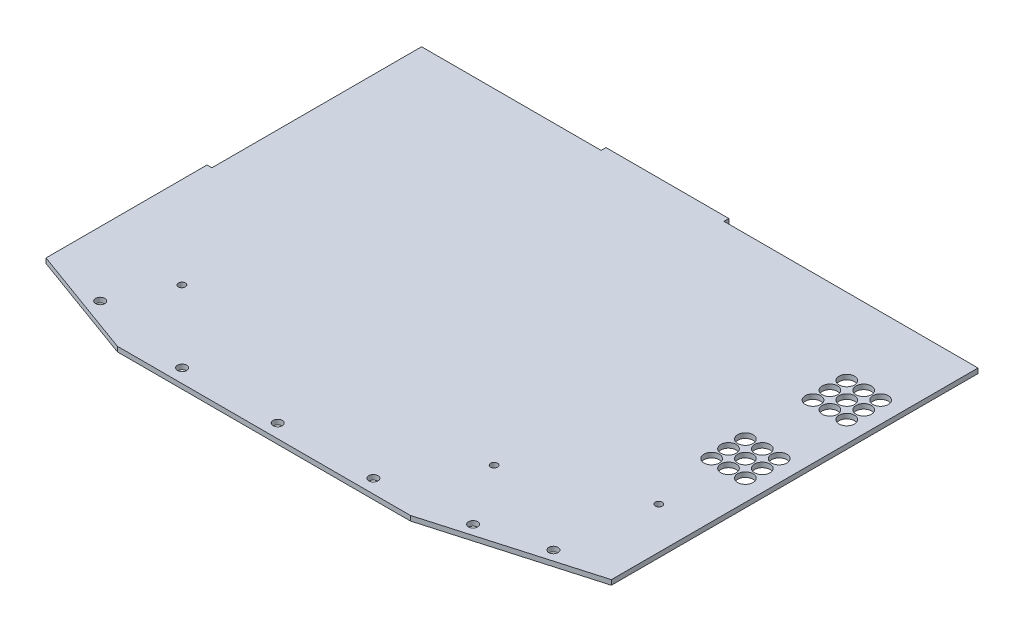
SolidWorks part; units mm, degrees
material "6061-T6 (SS)"
ref_plane "X-Y Datum" through (0, 0, 0) normal (0, 0, 1) x (1, 0, 0)
ref_plane "X-Z Datum" through (0, 0, 0) normal (0, 1, 0) x (1, 0, 0)
ref_plane "Y-Z Datum" through (0, 0, 0) normal (1, 0, 0) x (0, 0, -1)
sketch "Sketch1" plane through (0, 0, 0) normal (0, 0, 1) x (1, 0, 0)
  line L1 (-154.0556, -1.5875) -> (154.0556, -1.5875)
  line L2 (-154.0556, -1.5875) -> (-154.0556, 1.5875)
  line L3 (-154.0556, 1.5875) -> (154.0556, 1.5875)
  line L4 (154.0556, -1.5875) -> (154.0556, 1.5875)
  line L5 (-154.0556, -1.5875) -> (154.0556, 1.5875) construction
  line L6 (-154.0556, 1.5875) -> (154.0556, -1.5875) construction
  point P0 (0, 0)
  dimension "D1" = 3.175
  dimension "D2" = 308.1112
extrude "Boss-Extrude1" add sketch "Sketch1" along normal blind 267.83
sketch "Sketch3" plane through (154.0556, 0, 0) normal (1, 0, 0) x (0, 0, -1)
  line L9 (0, -1.5875) -> (0, 1.5875)
  line L10 (0, 1.5875) -> (-267.83, 1.5875)
  line L11 (-267.83, 1.5875) -> (-267.83, -1.5875)
  line L12 (-267.83, -1.5875) -> (0, -1.5875)
  line L13 (0, -1.5875) -> (0, 1.5875)
  line L14 (0, 1.5875) -> (-267.83, 1.5875)
  line L15 (-267.83, 1.5875) -> (-267.83, -1.5875)
  line L16 (-267.83, -1.5875) -> (0, -1.5875)
  dimension "D1" = 0
extrude "Boss-Extrude3" add sketch "Sketch3" along normal blind 3.175
sketch "Sketch4" plane through (0, 0, 267.83) normal (0, 0, 1) x (1, 0, 0)
  line L1 (157.2306, -1.5875) -> (208.1043, -1.5875)
  line L2 (157.2306, -1.5875) -> (157.2306, 1.5875)
  line L3 (157.2306, 1.5875) -> (208.1043, 1.5875)
  line L4 (208.1043, -1.5875) -> (208.1043, 1.5875)
  dimension "D1" = 3.175
  dimension "D2" = 50.8737
extrude "Boss-Extrude4" add sketch "Sketch4" against normal blind 267.83
sketch "Sketch6" plane through (0, 1.5875, 0) normal (0, 1, 0) x (1, 0, 0)
  line L0 (106.5043, -267.83) -> (106.5043, -223.38)
  line L1 (208.1043, -267.83) -> (-154.0556, -267.83) construction
  line L2 (208.1043, -223.38) -> (106.5043, -223.38)
  line L3 (208.1043, 0) -> (208.1043, -267.83) construction
  line L5 (106.5043, -267.83) -> (208.1047, -238.62)
  line L6 (208.1043, -223.38) -> (208.1047, -238.62)
  line M9 (-154.0556, -267.83) -> (208.1043, -267.83)
  line M10 (208.1043, -267.83) -> (208.1043, 0)
  dimension "D1" = 44.45
  dimension "D2" = 101.6
  dimension "D3" = 15.24
extrude "Cut-Extrude1" cut sketch "Sketch6" against normal through all contours L5 M9 M10 region at (174.2376, 1.5875, 258.0934)
sketch "Sketch11" plane through (0, -1.5875, 0) normal (0, -1, 0) x (1, 0, 0)
  line L0 (-84.2056, 267.83) -> (-84.2056, 242.43)
  line L1 (-154.0556, 267.83) -> (106.5043, 267.83) construction
  line L2 (-154.0556, 242.43) -> (-84.2056, 242.43)
  line L3 (-154.0556, 267.83) -> (-154.0556, 0) construction
  line L4 (-154.0556, 242.43) -> (-84.2056, 267.83)
  line M4 (-154.0556, 267.83) -> (-154.0556, 0)
  line M18 (106.5043, 267.83) -> (-154.0556, 267.83)
  dimension "D1" = 69.85
  dimension "D2" = 25.4
extrude "Cut-Extrude3" cut sketch "Sketch11" against normal through all contours L4 M4 M18 region at (-130.7723, -1.5875, 259.3633)
sketch "Sketch17" plane through (-154.0556, 0, 0) normal (-1, 0, 0) x (0, 0, 1)
  line L0 (136.4994, 1.5875) -> (136.4994, -1.5875)
  line L5 (242.43, 1.5875) -> (136.4994, 1.5875)
  line L9 (242.43, -1.5875) -> (0, -1.5875) construction
  line L10 (136.4994, -1.5875) -> (242.43, -1.5875)
  line L11 (242.43, -1.5875) -> (242.43, 1.5875)
extrude "Boss-Extrude5" add sketch "Sketch17" along normal blind 3.175
sketch "Sketch23" plane through (0, 1.5875, 0) normal (0, 1, 0) x (1, 0, 0)
  line L0 (-154.0556, -242.43) -> (-157.2306, -241.2755)
  line L1 (-157.2306, -242.43) -> (-157.2306, -136.4994) construction
  line L2 (-154.0556, -242.43) -> (-84.2056, -267.83) construction
  line L3 (-154.0556, -242.43) -> (-84.2056, -267.83) construction
extrude "Cut-Extrude7" cut sketch "Sketch23" against normal through all and the other way through all
sketch "Sketch25" plane through (0, -1.5875, 0) normal (0, -1, 0) x (1, 0, 0)
  line L0 (-157.2306, 241.2755) -> (-83.9957, 267.9063) construction
  line L1 (-50.9757, 267.83) -> (-50.9757, 258.94)
  line L2 (-157.2306, 241.2755) -> (-84.2056, 267.83) construction
  line L3 (-118.0827, 255.5111) -> (-115.3206, 247.9154)
  line L4 (-157.2306, 136.4994) -> (-157.2306, 241.2755) construction
  line L5 (-84.2056, 267.83) -> (106.5043, 267.83) construction
  line L6 (-50.9757, 258.94) -> (11.2543, 258.94) construction
  line L7 (11.2543, 258.94) -> (73.4843, 258.94) construction
  line L8 (172.5443, 248.8436) -> (172.5443, 240.7613)
  line L9 (106.5043, 267.83) -> (208.1043, 238.6201) construction
  line L10 (172.5443, 240.7613) -> (131.9043, 252.4453) construction
  circle A0 centre (-115.3206, 247.9154) radius 3
  circle A1 centre (-50.9757, 258.94) radius 3
  circle A2 centre (11.2543, 258.94) radius 3
  circle A3 centre (73.4843, 258.94) radius 3
  circle A4 centre (172.5443, 240.7613) radius 3
  circle A5 centre (131.9043, 252.4453) radius 3
  dimension "D2" = 90
  dimension "D3" = 6
  dimension "D13" = 8.89
  dimension "D1" = 8.0823
  dimension "D4" = 41.91
  dimension "D5" = 33.02
  dimension "D6" = 62.23
  dimension "D7" = 62.23
  dimension "D8" = 33.02
  dimension "D9" = 35.56
  dimension "D10" = 73.96
  dimension "D11" = 40.64
  dimension "D12" = 8.0823
extrude "Cut-Extrude8" cut sketch "Sketch25" against normal blind 3.175 contours A0 | A1 | A2 | A5 | A4 | A3 region at (-116.993, -1.5875, 245.5277) region at (-53.0371, -1.5875, 256.8787) region at (11.2543, -1.5875, 258.94) region at (170.4829, -1.5875, 238.7) region at (131.9043, -1.5875, 252.4453)
sketch "Sketch27" plane through (0, -1.5875, 0) normal (0, -1, 0) x (1, 0, 0)
  circle A0 centre (172.4867, 137.7748) radius 5 construction
  circle A1 centre (172.4867, 137.7748) radius 5
  circle A2 centre (183.4867, 137.7748) radius 5 construction
  circle A3 centre (183.4867, 137.7748) radius 5
  circle A4 centre (194.4867, 137.7748) radius 5 construction
  circle A5 centre (194.4867, 126.7748) radius 5 construction
  circle A6 centre (194.4867, 115.7748) radius 5 construction
  circle A7 centre (183.4867, 126.7748) radius 5 construction
  circle A8 centre (183.4867, 115.7748) radius 5 construction
  circle A9 centre (172.4867, 115.7748) radius 5 construction
  circle A10 centre (172.4867, 126.7748) radius 5 construction
  circle A11 centre (194.4867, 137.7748) radius 5
  circle A12 centre (194.4867, 126.7748) radius 5
  circle A13 centre (194.4867, 115.7748) radius 5
  circle A14 centre (183.4867, 126.7748) radius 5
  circle A15 centre (183.4867, 115.7748) radius 5
  circle A16 centre (172.4867, 115.7748) radius 5
  circle A17 centre (172.4867, 126.7748) radius 5
  circle A18 centre (194.4867, 71.7748) radius 5 construction
  circle A19 centre (194.4867, 60.7748) radius 5 construction
  circle A20 centre (194.4867, 49.7748) radius 5 construction
  circle A21 centre (183.4867, 71.7748) radius 5 construction
  circle A22 centre (183.4867, 60.7748) radius 5 construction
  circle A23 centre (183.4867, 49.7748) radius 5 construction
  circle A24 centre (172.4867, 49.7748) radius 5 construction
  circle A25 centre (172.4867, 60.7748) radius 5 construction
  circle A26 centre (172.4867, 71.7748) radius 5 construction
  circle A27 centre (194.4867, 71.7748) radius 5
  circle A28 centre (194.4867, 60.7748) radius 5
  circle A29 centre (194.4867, 49.7748) radius 5
  circle A30 centre (183.4867, 71.7748) radius 5
  circle A31 centre (183.4867, 60.7748) radius 5
  circle A32 centre (183.4867, 49.7748) radius 5
  circle A33 centre (172.4867, 49.7748) radius 5
  circle A34 centre (172.4867, 60.7748) radius 5
  circle A35 centre (172.4867, 71.7748) radius 5
extrude "Cut-Extrude9" cut sketch "Sketch27" against normal through all
sketch "Sketch28" plane through (0, -1.5875, 0) normal (0, -1, 0) x (1, 0, 0)
  point P0 (180.965, 180.586)
  point P1 (105.429, 212.285)
  point P3 (-97.7709, 212.285)
hole_wizard "M4 Clearance Hole1" positions "Sketch28" profile "Sketch29" hole size "M4" standard "ANSI Metric" end condition through all
sketch "Sketch29" plane through (180.965, -1.5875, 180.586) normal (1, 0, 0) x (0, 0, -1)
  line L0 (0, 0) -> (0, 3.175)
  line L1 (0, 3.175) -> (2.25, 3.175)
  line L2 (2.25, 3.175) -> (2.25, 0)
  line L5 (2.25, 0) -> (0, 0)
  line L11 (0, -6.35) -> (0, 107.95) construction
  dimension "Thru Hole Dia." = 4.5
  dimension "Thru Hole Depth" = 3.175
sketch "Sketch30" plane through (0, 0, 0) normal (0, 0, -1) x (-1, 0, 0)
  line L0 (37.216, 1.5875) -> (37.216, -1.5875) construction
  line L1 (-42.784, 1.5875) -> (37.216, 1.5875) construction
  line L2 (-42.784, 1.5875) -> (-42.784, -1.5875) construction
  line L3 (37.216, 1.5875) -> (37.216, -1.5875)
  line L4 (-42.784, 1.5875) -> (37.216, 1.5875)
  line L5 (-42.784, 1.5875) -> (-42.784, -1.5875)
  line L6 (154.0556, -1.5875) -> (-208.1043, -1.5875) construction
  line L7 (154.0556, -1.5875) -> (-208.1043, -1.5875)
  line M1 (154.0556, 1.5875) -> (-208.1043, 1.5875)
  line M3 (-208.1043, -1.5875) -> (154.0556, -1.5875)
extrude "Boss-Extrude6" add sketch "Sketch30" along normal blind 3.175 contours L5 L3 M1 M3 region at (2.784, 0, 0)
